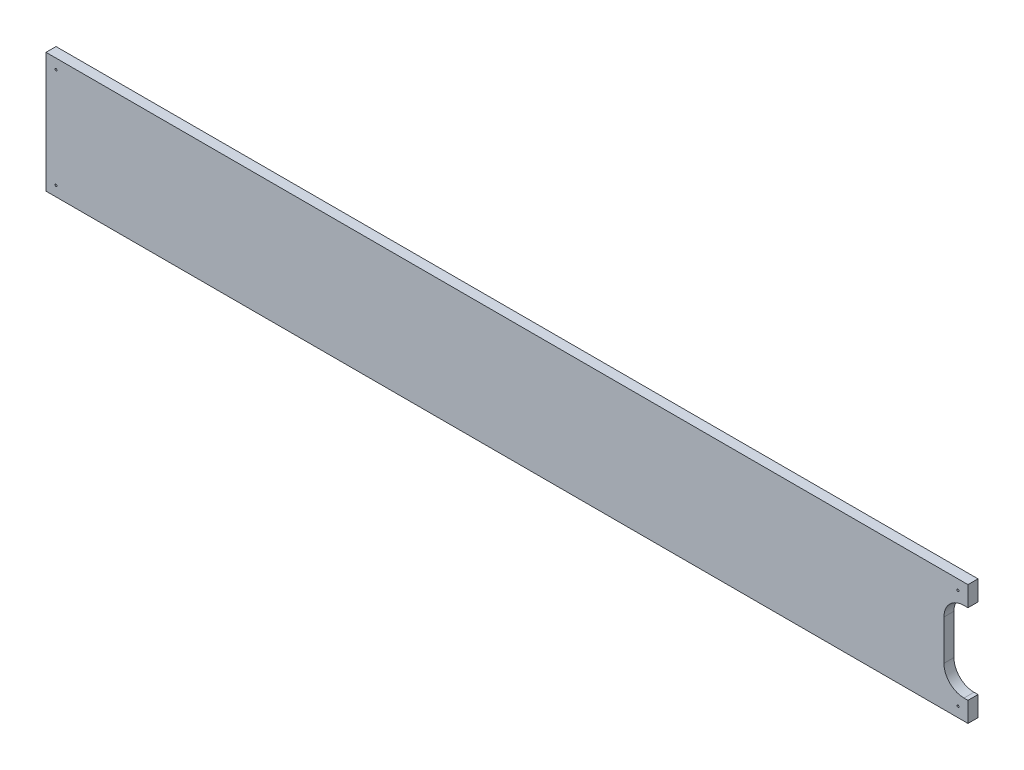
SolidWorks part; units mm, degrees
material "Contreplaqué pin"
ref_plane "Plan de face" through (0, 0, 0) normal (0, 0, 1) x (1, 0, 0)
ref_plane "Plan de dessus" through (0, 0, 0) normal (0, 1, 0) x (1, 0, 0)
ref_plane "Plan de droite" through (0, 0, 0) normal (1, 0, 0) x (0, 0, -1)
sketch "Esquisse1" plane through (0, 0, 0) normal (0, 0, 1) x (1, 0, 0)
  line L1 (0, 0) -> (460, 0)
  line L2 (0, 0) -> (0, 60)
  line L3 (0, 60) -> (460, 60)
  line L4 (460, 0) -> (460, 60)
  dimension "D1" = 460
  dimension "D2" = 60
extrude "Boss.-Extru.1" add sketch "Esquisse1" along normal blind 5
hole_wizard "Diamètre du perçage Ø1.0 (1)1" positions "Esquisse2" profile "Esquisse3" hole size "Ø1.0" standard "DIN" end condition through all
sketch "Esquisse2" plane through (0, 0, 5) normal (0, 0, 1) x (1, 0, 0)
  line L0 (0, 60) -> (0, 0) construction
  line L1 (460, 60) -> (0, 60) construction
  line L2 (460, 0) -> (460, 60) construction
  line L3 (0, 0) -> (460, 0) construction
  point P0 (5, 55)
  point P2 (5, 5)
  point P4 (455, 5)
  point P6 (455, 55)
  dimension "D1" = 5
  dimension "D2" = 5
  dimension "D3" = 5
  dimension "D4" = 5
sketch "Esquisse3" plane through (5, 55, 5) normal (1, 0, 0) x (0, -1, 0)
  line L0 (0, 0) -> (0, 5)
  line L1 (0, 5) -> (0.5, 5)
  line L2 (0.5, 5) -> (0.5, 0)
  line L5 (0.5, 0) -> (0, 0)
  line L11 (0, -6.35) -> (0, 107.95) construction
  dimension "Diamètre du perçage jusqu'au prochain" = 1
  dimension "Profondeur du perçage jusqu'au prochain" = 5
sketch "Esquisse4" plane through (0, 0, 5) normal (0, 0, 1) x (1, 0, 0)
  line L0 (460, 0) -> (460, 60) construction
  line L1 (460, 50) -> (458, 50)
  line L2 (460, 50) -> (460, 10)
  line L3 (460, 10) -> (458, 10)
  line L4 (448, 40) -> (448, 20)
  line L5 (460, 60) -> (0, 60) construction
  line L6 (0, 0) -> (460, 0) construction
  arc A0 (458, 10) -> (448, 20) centre (458, 20) cw
  arc A1 (448, 40) -> (458, 50) centre (458, 40) cw
  point P12 (448, 10)
  dimension "D4" = 10
  dimension "D1" = 12
  dimension "D2" = 10
  dimension "D3" = 10
extrude "Enlèv. mat.-Extru.1" cut sketch "Esquisse4" against normal up to next
